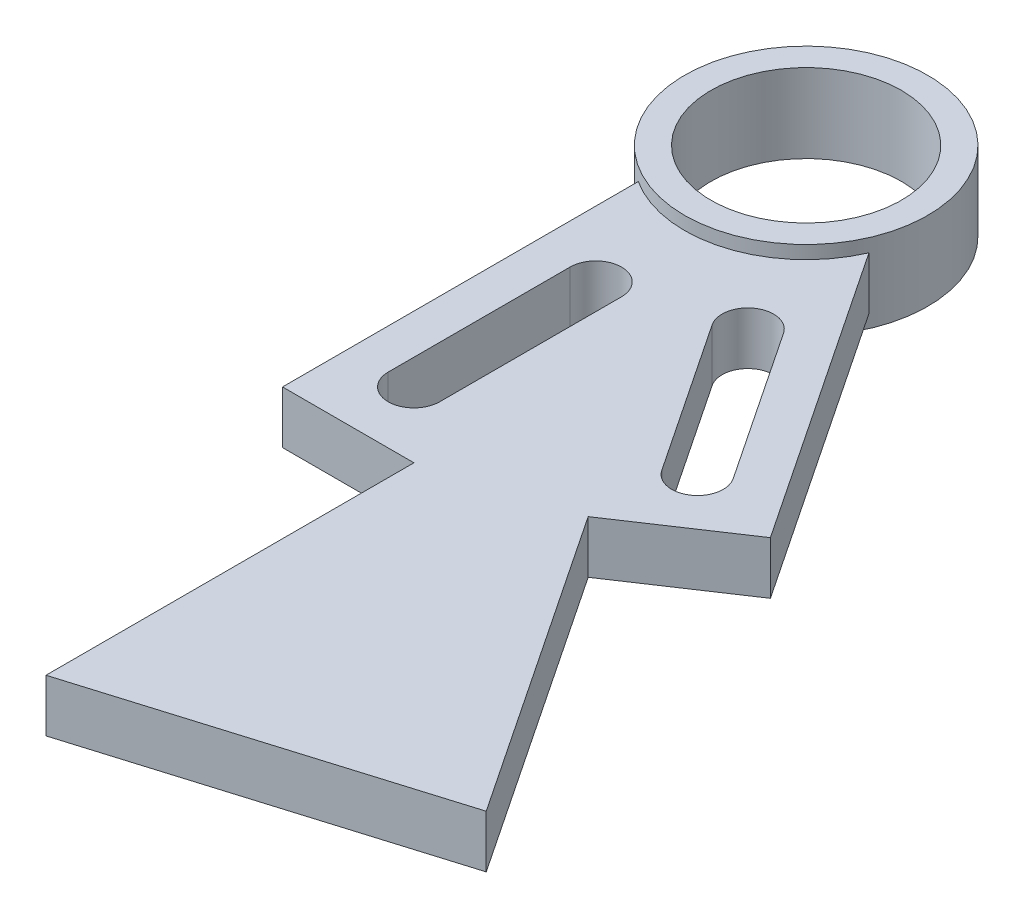
SolidWorks part; units mm, degrees
material "AISI 4130 Steel, normalized at 870C"
ref_plane "Front Plane" through (0, 0, 0) normal (0, 0, 1) x (1, 0, 0)
ref_plane "Top Plane" through (0, 0, 0) normal (0, 1, 0) x (1, 0, 0)
ref_plane "Right Plane" through (0, 0, 0) normal (1, 0, 0) x (0, 0, -1)
sketch "Sketch1" plane through (0, 0, 0) normal (0, 1, 0) x (1, 0, 0)
  line L0 (0, -50.4952) -> (0, -14.6812) construction
  line L1 (28.0186, -42.0086) -> (8.1463, -12.2138) construction
  line L2 (0, -47.3837) -> (0, -25.4127) construction
  line L5 (-3.1115, -47.3837) -> (-3.1115, -25.4127)
  line L8 (-7.9375, -55.3212) -> (7.9375, -55.3212)
  line L9 (24.093, -50.4278) -> (37.2999, -41.6192)
  line L10 (-7.9375, -55.3212) -> (-7.9375, -12.3505)
  line L11 (37.2999, -41.6192) -> (13.4564, -5.8704)
  line L12 (7.9375, -55.3212) -> (7.9375, -99.7712)
  line L13 (24.093, -50.4278) -> (48.7572, -87.4073)
  line L14 (7.9375, -99.7712) -> (48.7572, -87.4073)
  line L15 (0, -14.6812) -> (0, 0) construction
  line L16 (0, -55.3212) -> (0, -50.4952) construction
  line L17 (30.6964, -46.0235) -> (28.0186, -42.0086)
  line L18 (3.1115, -47.3837) -> (3.1115, -25.4127)
  line L19 (14.1009, -21.1417) -> (26.2921, -39.42) construction
  line L20 (16.6895, -19.4152) -> (28.8807, -37.6936)
  line L21 (11.5124, -22.8682) -> (23.7035, -41.1465)
  line L22 (8.1463, -12.2138) -> (0, 0) construction
  line L23 (0, 0) -> (19.144, -63.2043) construction
  line L25 (173.8477, -260.6519) -> (14.541, -21.8014) construction
  line L27 (0, 0) -> (28.3474, -93.5892) construction
  circle A0 centre (0, 0) radius 11.5062
  circle A1 centre (0, 0) radius 14.6812
  arc A2 (-3.1115, -47.3837) -> (3.1115, -47.3837) centre (0, -47.3837) ccw
  arc A3 (3.1115, -25.4127) -> (-3.1115, -25.4127) centre (0, -25.4127) ccw
  arc A4 (16.6895, -19.4152) -> (11.5124, -22.8682) centre (14.1009, -21.1417) ccw
  arc A5 (23.7035, -41.1465) -> (28.8807, -37.6936) centre (26.2921, -39.42) ccw
  point P9 (0, -36.3982)
  point P14 (20.1965, -30.2809)
  point P23 (0, -55.3212)
  point P26 (30.6964, -46.0235)
  point P33 (0, -50.4952)
  point P36 (28.0186, -42.0086)
  point P38 (0, -22.3012)
  dimension "D2" = 29.3624
  dimension "D3" = 40.64
  dimension "D4" = 4.826
  dimension "D6" = 44.45
  dimension "D7" = 7.9375
  dimension "D5" = 4.826
  dimension "D8" = 7.62
  dimension "D9" = 66.04
extrude "Bearing extrude" add sketch "Sketch1" along normal mid plane 9.525 contours A1 A0 region at (-6.8368, 0, -12.521)
extrude "Boss-Extrude2" add sketch "Sketch1<5>" along normal mid plane 6.35 contours A1 L10 L8 L12 L14 L13 L9 L11 A4 A2 region at (16.9968, 0, 56.1152)
sketch "Sketch1<5>" plane through (0, 0, 0) normal (0, 1, 0) x (1, 0, 0) same geometry as "Sketch1"
sketch3d "Tab Point"
  line L0 (19.144, 0, 63.2043) -> (19.144, 25.4, 63.2043) construction
  line L1 (0, 0, 0) -> (19.144, 0, 63.2043) construction
  line L2 (0, 0, 0) -> (28.3474, 0, 93.5892) construction
  dimension "D1" = 25.4
equation "\"Apex_thickness\"= .25"
equation "\"Bearing_diameter\"= .906"
equation "\"A-arm_angle\"= 32.91"
equation "\"D1@Sketch1\"=\"Bearing_diameter\""
equation "\"D1@Boss-Extrude2\"= \"Apex_thickness\""
equation "\"apex slot\"= 1.4"
equation "\"tube diameter\"= 5 / 8"
